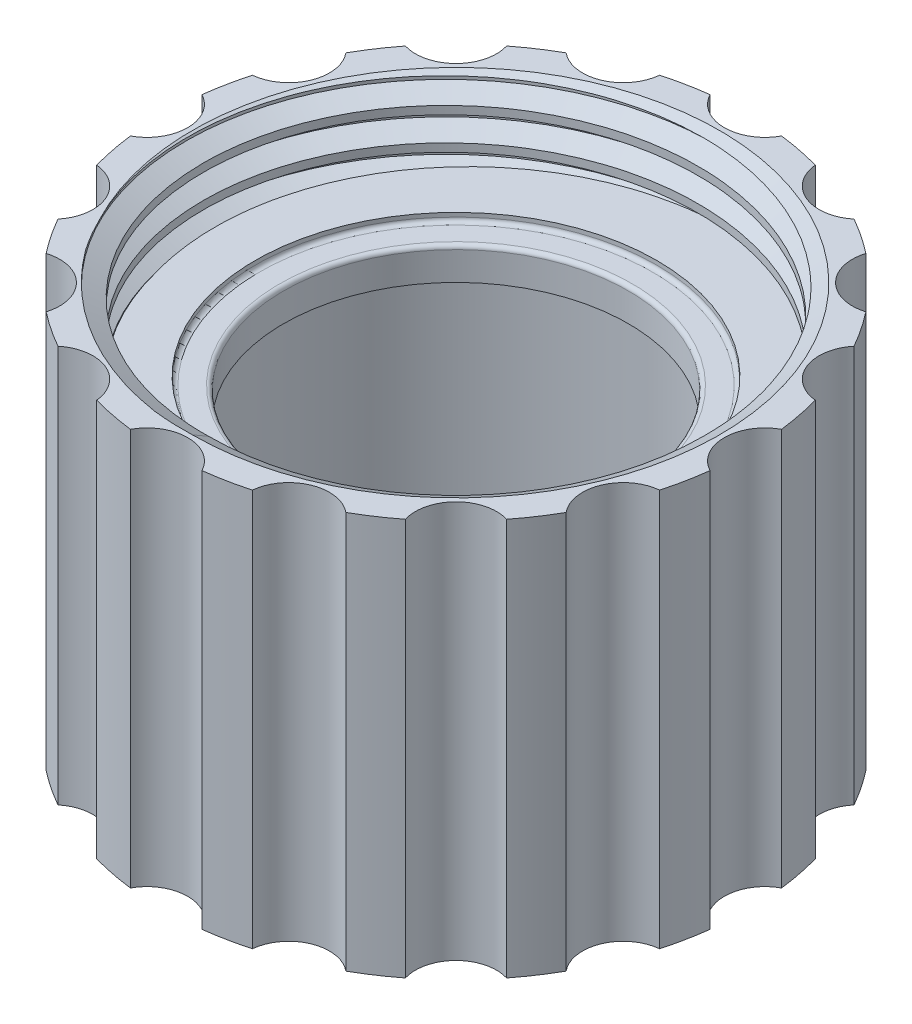
SolidWorks part; units mm, degrees
ref_plane "Front Plane" through (0, 0, 0) normal (0, 0, 1) x (1, 0, 0)
ref_plane "Top Plane" through (0, 0, 0) normal (0, 1, 0) x (1, 0, 0)
ref_plane "Right Plane" through (0, 0, 0) normal (1, 0, 0) x (0, 0, -1)
sketch "Sketch1" plane through (0, 0, 0) normal (0, 0, 1) x (1, 0, 0)
  line L0 (0, 0) -> (0, -186.4138) construction
  line L1 (-15.25, -172.1515) -> (-15.25, -177.1515)
  line L2 (-15.25, -177.1515) -> (-12.375, -177.1515)
  line L3 (-15.25, -172.1515) -> (-18, -172.1515)
  line L4 (-18, -172.1515) -> (-18, -196.6395)
  line L5 (-12.125, -177.6515) -> (-10.875, -177.6515)
  line L6 (-12.375, -177.1515) -> (-12.375, -177.4015)
  line L7 (-10.625, -177.9015) -> (-10.625, -179.6515)
  line L8 (-10.625, -179.6515) -> (-13, -179.6515)
  line L9 (-13, -179.6515) -> (-13, -196.6395)
  line L10 (-13, -196.6395) -> (-18, -196.6395)
  arc A0 (-12.375, -177.4015) -> (-12.125, -177.6515) centre (-12.125, -177.4015) ccw
  arc A1 (-10.625, -177.9015) -> (-10.875, -177.6515) centre (-10.875, -177.9015) ccw
  dimension "D1" = 30.5
  dimension "D4" = 0.25
  dimension "D6" = 0.25
  dimension "D2" = 36
  dimension "D3" = 24.75
  dimension "D5" = 0.5
  dimension "D7" = 21.25
  dimension "D8" = 5
  dimension "D9" = 2
  dimension "D10" = 5
revolve "Revolve1" add sketch "Sketch1" angle 360 about L0
chamfer "Chamfer1" distance 1 angle 30 1 edges at (0, -172.1515, 15.25) first distance on face at (0, -172.1515, 18)
thread "Thread1" pitch 2 method cut trim with start face yes trim with end face yes profile "Thread Profile2" start angle 0, offset 5, length 0, pitch 2, diameter 30.5
ref_plane "Plane2" through (-15.25, -167.7289, 0) normal (0, 0, 1) x (-1, 0, 0)
sketch "Thread Profile2" plane through (-15.25, -167.7289, 0) normal (0, 0, 1) x (-1, 0, 0)
  line L0 (0, 0) -> (0, 2) construction
  line L1 (0, 0) -> (1.0825, 0.625)
  line L2 (1.0825, 0.625) -> (1.0825, 0.875)
  line L3 (1.0825, 0.875) -> (0, 1.5)
  line L4 (1.0825, 0.75) -> (0, 0.75) construction
  line L11 (0, 0) -> (0, 1.5)
  point P2 (0, 0)
  dimension "Pitch" = 2
  dimension "Profile_Angle" = 60
  dimension "Profile_Land" = 0.25
  dimension "Profile_Height" = 1.0825
sketch "Sketch6" plane through (0, -196.6395, 0) normal (0, -1, 0) x (1, 0, 0)
  line L0 (0, 0) -> (0, 21.3657) construction
  arc A0 (-2.2056, 17.8644) -> (2.2056, 17.8644) centre (0, 19.0414) ccw
  circle A1 centre (0, 0) radius 18 construction
  arc A2 (-2.2056, 17.8644) -> (2.2056, 17.8644) centre (0, 0) cw
  arc A3 (4.7987, 17.3486) -> (8.8741, 15.6605) centre (0, 0) cw
  arc A4 (4.7987, 17.3486) -> (8.8741, 15.6605) centre (7.2868, 17.592) ccw
  arc A5 (11.0724, 14.1916) -> (14.1916, 11.0724) centre (0, 0) cw
  arc A6 (11.0724, 14.1916) -> (14.1916, 11.0724) centre (13.4643, 13.4643) ccw
  arc A7 (15.6605, 8.8741) -> (17.3486, 4.7987) centre (0, 0) cw
  arc A8 (15.6605, 8.8741) -> (17.3486, 4.7987) centre (17.592, 7.2868) ccw
  arc A9 (17.8644, 2.2056) -> (17.8644, -2.2056) centre (0, 0) cw
  arc A10 (17.8644, 2.2056) -> (17.8644, -2.2056) centre (19.0414, 0) ccw
  arc A11 (17.3486, -4.7987) -> (15.6605, -8.8741) centre (0, 0) cw
  arc A12 (17.3486, -4.7987) -> (15.6605, -8.8741) centre (17.592, -7.2868) ccw
  arc A13 (14.1916, -11.0724) -> (11.0724, -14.1916) centre (0, 0) cw
  arc A14 (14.1916, -11.0724) -> (11.0724, -14.1916) centre (13.4643, -13.4643) ccw
  arc A15 (8.8741, -15.6605) -> (4.7987, -17.3486) centre (0, 0) cw
  arc A16 (8.8741, -15.6605) -> (4.7987, -17.3486) centre (7.2868, -17.592) ccw
  arc A17 (2.2056, -17.8644) -> (-2.2056, -17.8644) centre (0, 0) cw
  arc A18 (2.2056, -17.8644) -> (-2.2056, -17.8644) centre (0, -19.0414) ccw
  arc A19 (-4.7987, -17.3486) -> (-8.8741, -15.6605) centre (0, 0) cw
  arc A20 (-4.7987, -17.3486) -> (-8.8741, -15.6605) centre (-7.2868, -17.592) ccw
  arc A21 (-11.0724, -14.1916) -> (-14.1916, -11.0724) centre (0, 0) cw
  arc A22 (-11.0724, -14.1916) -> (-14.1916, -11.0724) centre (-13.4643, -13.4643) ccw
  arc A23 (-15.6605, -8.8741) -> (-17.3486, -4.7987) centre (0, 0) cw
  arc A24 (-15.6605, -8.8741) -> (-17.3486, -4.7987) centre (-17.592, -7.2868) ccw
  arc A25 (-17.8644, -2.2056) -> (-17.8644, 2.2056) centre (0, 0) cw
  arc A26 (-17.8644, -2.2056) -> (-17.8644, 2.2056) centre (-19.0414, 0) ccw
  arc A27 (-17.3486, 4.7987) -> (-15.6605, 8.8741) centre (0, 0) cw
  arc A28 (-17.3486, 4.7987) -> (-15.6605, 8.8741) centre (-17.592, 7.2868) ccw
  arc A29 (-14.1916, 11.0724) -> (-11.0724, 14.1916) centre (0, 0) cw
  arc A30 (-14.1916, 11.0724) -> (-11.0724, 14.1916) centre (-13.4643, 13.4643) ccw
  arc A31 (-8.8741, 15.6605) -> (-4.7987, 17.3486) centre (0, 0) cw
  arc A32 (-8.8741, 15.6605) -> (-4.7987, 17.3486) centre (-7.2868, 17.592) ccw
  point P56 (0, 0)
  circle M5 centre (0, 0) radius 18
  dimension "D1" = 2.5
  dimension "D2" = 16
extrude "Cut-Extrude1" cut sketch "Sketch6" against normal through all both and the other way through all contours A4 M5 | A6 M5 | A8 M5 | A30 M5 | A28 M5 | A26 M5 | A24 M5 | A22 M5 | A18 M5 | A16 M5 | A14 M5 | A12 M5 | A10 M5 | A2 A0 | A31 A32 | A19 A20 region at (6.6485, -196.6395, 16.0509) region at (-12.2848, -196.6395, 12.2848) region at (12.2848, -196.6395, 12.2848) region at (-16.0509, -196.6395, 6.6485) region at (16.0509, -196.6395, 6.6485) region at (-17.3733, -196.6395, 0) region at (17.3733, -196.6395, 0) region at (-16.0509, -196.6395, -6.6485) region at (16.0509, -196.6395, -6.6485) region at (-12.2848, -196.6395, -12.2848) region at (12.2848, -196.6395, -12.2848) region at (6.6485, -196.6395, -16.0509) region at (0, -196.6395, -17.3733)
